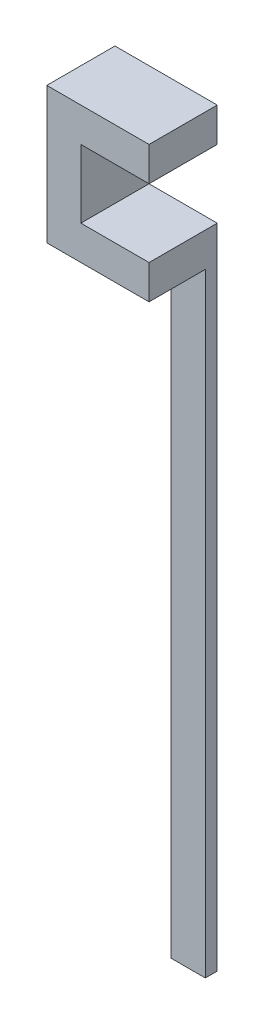
SolidWorks part; units mm, degrees
ref_plane "Front Plane" through (0, 0, 0) normal (0, 0, 1) x (1, 0, 0)
ref_plane "Top Plane" through (0, 0, 0) normal (0, 1, 0) x (1, 0, 0)
ref_plane "Right Plane" through (0, 0, 0) normal (1, 0, 0) x (0, 0, -1)
sketch "Sketch1" plane through (0, 0, 0) normal (0, 0, 1) x (1, 0, 0)
  line L9 (0, 10.8119) -> (0, -9.1881)
  line L10 (0, -9.1881) -> (15, -9.1881)
  line L11 (15, -9.1881) -> (15, -4.1881)
  line L12 (15, -4.1881) -> (5, -4.1881)
  line L13 (0, 10.8119) -> (15, 10.8119)
  line L14 (15, 10.8119) -> (15, 5.8119)
  line L15 (15, 5.8119) -> (5, 5.8119)
  line L16 (5, 5.8119) -> (5, -4.1881)
  point P3 (0, 0.8119)
  dimension "D1" = 20
  dimension "D2" = 10
  dimension "D3" = 5
  dimension "D4" = 5
  dimension "D5" = 10
  dimension "D6" = 15
extrude "Boss-Extrude1" add sketch "Sketch1" along normal blind 10
sketch "Sketch3" plane through (0, -9.1881, 0) normal (0, -1, 0) x (-1, 0, 0)
  line L1 (-15, 0) -> (-10, 0)
  line L2 (-15, 0) -> (-15, -1.75)
  line L3 (-15, -1.75) -> (-10, -1.75)
  line L4 (-10, 0) -> (-10, -1.75)
  dimension "D1" = 5
  dimension "D2" = 1.75
extrude "Boss-Extrude2" add sketch "Sketch3" along normal blind 90
